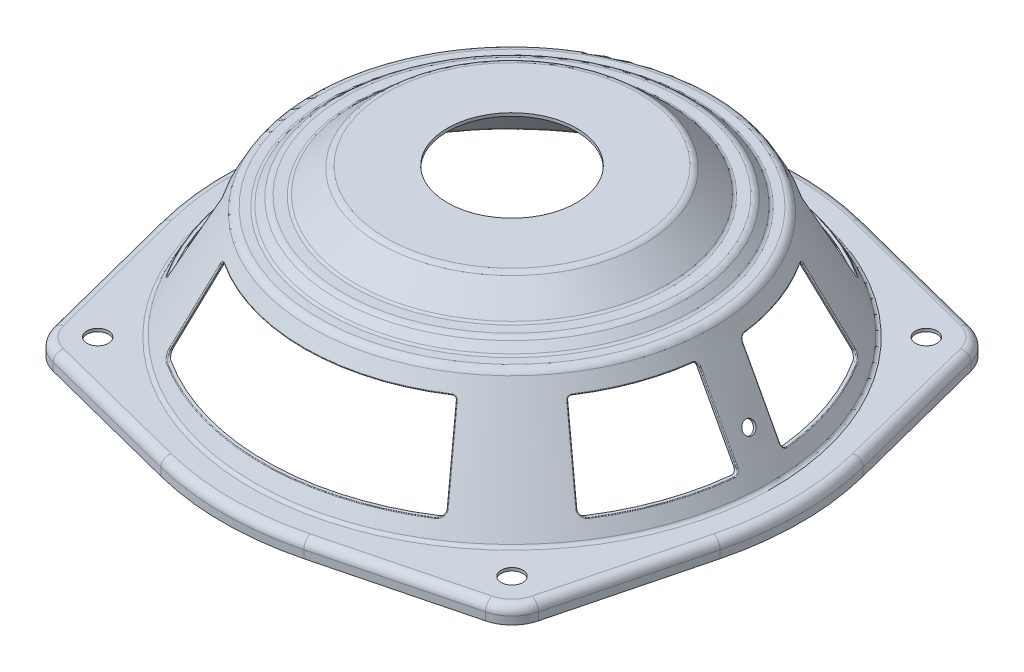
SolidWorks part; units mm, degrees
material "Простая углеродистая сталь"
ref_plane "Спереди" through (0, 0, 0) normal (0, 0, 1) x (1, 0, 0)
ref_plane "Сверху" through (0, 0, 0) normal (0, 1, 0) x (1, 0, 0)
ref_plane "Справа" through (0, 0, 0) normal (1, 0, 0) x (0, 0, -1)
sketch "Эскиз1" plane through (0, 0, 0) normal (0, 0, 1) x (1, 0, 0)
  line L0 (0, 0) -> (-30, 0)
  line L1 (-30, 0) -> (-36.5, -6)
  line L2 (-36.5, -6) -> (-40, -6)
  line L3 (-40, -6) -> (-42.5, -8.3077)
  line L4 (-42.5, -8.3077) -> (-46, -8.3077)
  line L5 (-46, -8.3077) -> (-60, -34.5)
  line L6 (-60, -34.5) -> (0, -34.5)
  line L7 (0, -34.5) -> (0, 0)
  dimension "D1" = 60
  dimension "D2" = 34.5
  dimension "D3" = 30
  dimension "D4" = 36.5
  dimension "D5" = 6
  dimension "D6" = 40
  dimension "D7" = 42.5
  dimension "D8" = 46
revolve "Повернуть1" add sketch "Эскиз1" angle 360 about L7
sketch "Эскиз2" plane through (0, -34.5, 0) normal (0, -1, 0) x (1, 0, 0)
  circle A0 centre (0, 0) radius 67
  dimension "D1" = 134
extrude "Бобышка-Вытянуть1" add sketch "Эскиз2" along normal blind 3.8
sketch "Эскиз3" plane through (0, -34.5, 0) normal (0, 1, 0) x (1, 0, 0)
  line L0 (-56.3181, -50.1899) -> (-64.9097, -16.6052)
  line L1 (-48.0833, 48.0833) -> (48.0833, 48.0833) construction
  line L2 (-48.0833, 48.0833) -> (-48.0833, -48.0833) construction
  line L3 (-48.0833, -48.0833) -> (48.0833, -48.0833) construction
  line L4 (48.0833, 48.0833) -> (48.0833, -48.0833) construction
  line L5 (-48.0833, 48.0833) -> (48.0833, -48.0833) construction
  line L6 (-48.0833, -48.0833) -> (48.0833, 48.0833) construction
  line L7 (-64.9097, 16.6052) -> (-56.3181, 50.1899)
  line L8 (-16.6052, 64.9097) -> (-50.1899, 56.3181)
  line L9 (50.1899, 56.3181) -> (16.6052, 64.9097)
  line L10 (56.3181, 50.1899) -> (64.9097, 16.6052)
  line L11 (64.9097, -16.6052) -> (56.3181, -50.1899)
  line L12 (16.6052, -64.9097) -> (50.1899, -56.3181)
  line L13 (-16.6052, -64.9097) -> (-50.1899, -56.3181)
  arc A0 (-56.3181, -50.1899) -> (-50.1899, -56.3181) centre (-48.0833, -48.0833) ccw
  arc A2 (64.9097, -16.6052) -> (64.9097, 16.6052) centre (0, 0) ccw
  arc A3 (-50.1899, 56.3181) -> (-56.3181, 50.1899) centre (-48.0833, 48.0833) ccw
  circle A4 centre (0, 0) radius 67 construction
  arc A5 (-16.6052, -64.9097) -> (16.6052, -64.9097) centre (0, 0) ccw
  arc A6 (-64.9097, 16.6052) -> (-64.9097, -16.6052) centre (0, 0) ccw
  arc A7 (16.6052, 64.9097) -> (-16.6052, 64.9097) centre (0, 0) ccw
  arc A8 (50.1899, -56.3181) -> (56.3181, -50.1899) centre (48.0833, -48.0833) ccw
  arc A9 (56.3181, 50.1899) -> (50.1899, 56.3181) centre (48.0833, 48.0833) ccw
  point P0 (0, 0)
  dimension "D1" = 8.5
  dimension "D2" = 136
extrude "Бобышка-Вытянуть2" add sketch "Эскиз3" against normal up to surface (3.8 mm away) up to face at (0, -38.3, -67)
sketch "Эскиз4" plane through (0, -38.3, 0) normal (0, -1, 0) x (1, 0, 0)
  circle A0 centre (-48.0833, 48.0833) radius 2.5
  circle A1 centre (48.0833, 48.0833) radius 2.5
  circle A2 centre (48.0833, -48.0833) radius 2.5
  circle A3 centre (-48.0833, -48.0833) radius 2.5
  dimension "D1" = 5
  dimension "D2" = 136
extrude "Вырез-Вытянуть1" cut sketch "Эскиз4" against normal through all
fillet "Скругление1" radius 2 19 edges at (-67, -34.5, 0) (-60.6139, -34.5, -33.3975) (-54.0937, -34.5, -54.0937) (-33.3975, -34.5, -60.6139) (0, -34.5, -67) (33.3975, -34.5, -60.6139) (54.0937, -34.5, -54.0937) (60.6139, -34.5, -33.3975) (67, -34.5, 0) (60.6139, -34.5, 33.3975) (54.0937, -34.5, 54.0937) (33.3975, -34.5, 60.6139) (0, -34.5, 67) (-33.3975, -34.5, 60.6139) (-54.0937, -34.5, 54.0937) (-60.6139, -34.5, 33.3975) (0, -8.3077, -46) (0, -6, -40) (0, 0, -30)
fillet "Скругление2" radius 1 3 edges at (0, -34.5, -60) (0, -8.3077, -42.5) (0, -6, -36.5)
shell "Оболочка1" thickness 0.7 removed face at (48.0833, -38.3, -50.5833) removed face at (48.0833, -38.3, 45.5833) removed face at (-48.0833, -38.3, -50.5833) removed face at (-48.0833, -38.3, 45.5833) removed face at (-48.0833, -38.3, -50.5833)
sketch "Эскиз5" plane through (0, 0, 0) normal (0, 0, 1) x (1, 0, 0)
  line L0 (-32.5, -30.8) -> (-27, -12.8)
  line L1 (-27, -12.8) -> (27, -12.8)
  line L2 (27, -12.8) -> (32.5, -30.8)
  line L3 (32.5, -30.8) -> (-32.5, -30.8)
  line L4 (-16.6052, -38.3) -> (16.6052, -38.3) construction
  point P2 (0, -12.8)
  point P5 (0, -30.8)
  dimension "D1" = 7.5
  dimension "D2" = 18
  dimension "D3" = 54
  dimension "D4" = 65
extrude "Вырез-Вытянуть2" cut sketch "Эскиз5" against normal up to next and the other way up to next
sketch "Эскиз6" plane through (0, 0, 0) normal (1, 0, 0) x (0, 0, -1)
  line L0 (-27, -12.8) -> (27, -12.8)
  line L1 (27, -12.8) -> (32.5, -30.8)
  line L2 (32.5, -30.8) -> (-32.5, -30.8)
  line L3 (-32.5, -30.8) -> (-27, -12.8)
  line L6 (57.2286, -30.8) -> (47.1048, -30.8) construction
  line L7 (39.2106, -12.8) -> (47.6075, -12.8) construction
  point P2 (0, -12.8)
  point P5 (0, -30.8)
  dimension "D1" = 54
  dimension "D2" = 65
extrude "Вырез-Вытянуть3" cut sketch "Эскиз6" against normal up to next
sketch "Эскиз7" plane through (0, 0, 0) normal (1, 0, 0) x (0, 0, -1)
  line L0 (-27, -12.8) -> (-5, -12.8)
  line L1 (-5, -12.8) -> (-5, -30.8)
  line L2 (-5, -30.8) -> (-32.5, -30.8)
  line L3 (-32.5, -30.8) -> (-27, -12.8)
  line L4 (5, -12.8) -> (27, -12.8)
  line L5 (27, -12.8) -> (32.5, -30.8)
  line L6 (32.5, -30.8) -> (5, -30.8)
  line L7 (5, -30.8) -> (5, -12.8)
  line L8 (-5, -12.8) -> (5, -12.8) construction
  line L11 (-48.4012, -12.8) -> (-40.1706, -12.8) construction
  line L12 (-47.1048, -30.8) -> (-57.2286, -30.8) construction
  point P6 (0, -12.8)
  dimension "D1" = 54
  dimension "D2" = 65
  dimension "D3" = 10
extrude "Вырез-Вытянуть4" cut sketch "Эскиз7" along normal up to next
sketch "Эскиз8" plane through (0, 0, 0) normal (0, 1, 0) x (1, 0, 0)
  circle A0 centre (0, 0) radius 15
  dimension "D1" = 30
extrude "Вырез-Вытянуть5" cut sketch "Эскиз8" against normal through all
fillet "Скругление3" radius 1 20 edges at (27, -12.8, -39.6906) (32.5, -30.8, -47.5854) (-32.5, -30.8, -47.5854) (-27, -12.8, -39.6906) (-27, -12.8, 39.6906) (27, -12.8, 39.6906) (32.5, -30.8, 47.5854) (-32.5, -30.8, 47.5854) (39.6906, -12.8, 27) (47.7432, -12.8, -5) (39.6906, -12.8, -27) (47.7432, -12.8, 5) (57.4081, -30.8, 5) (47.5854, -30.8, -32.5) (57.4081, -30.8, -5) (47.5854, -30.8, 32.5) (-47.5854, -30.8, -32.5) (-39.6906, -12.8, -27) (-39.6906, -12.8, 27) (-47.5854, -30.8, 32.5)
fillet "Скругление4" radius 0.2 40 edges at (31.9024, -30.4573, -48.2452) (0, -30.8, -58.0223) (-32.059, -30.2142, -47.9852) (47.9852, -30.2142, -32.059) (48.2424, -13.0532, -5.3349) (57.5903, -30.4346, -5.2271) (54.7942, -30.8, -19.0837) (-31.9024, -30.4573, 48.2452) (0, -30.8, 58.0223) (32.059, -30.2142, 47.9852) (-48.2452, -30.4573, -31.9024) (-58.0223, -30.8, 0) (-47.9852, -30.2142, 32.059) (57.6128, -30.4839, 5.2704) (48.2003, -12.991, 5.4123) (48.2452, -30.4573, 31.9024) (54.7942, -30.8, 19.0837) (40.4047, -12.9616, -26.805) (45.4854, -12.8, -16.5455) (26.805, -12.9616, 40.4047) (0, -12.8, 48.4012) (-26.9427, -13.0694, 40.3822) (-26.805, -12.9616, -40.4047) (0, -12.8, -48.4012) (26.9427, -13.0694, -40.3822) (-40.3822, -13.0694, -26.9427) (-40.4047, -12.9616, 26.805) (-48.4012, -12.8, 0) (45.4854, -12.8, 16.5455) (40.3822, -13.0694, 26.9427)
ref_plane "Плоскость1" through (31.4136, 16.8683, 0) normal (0.881, 0.4731, 0) x (0, 0, -1)
sketch "Эскиз9" plane through (31.4136, 16.8683, 0) normal (0.881, 0.4731, 0) x (0, 0, -1)
  line L0 (-5, -44.1687) -> (5, -44.1687) construction
  line L1 (-5, -35.0892) -> (-5, -53.2482) construction
  line L2 (5, -53.2482) -> (5, -35.0892) construction
  line L3 (5, -44.1687) -> (0, -48.1687) construction
  line L4 (0, -48.1687) -> (0, -44.1687) construction
  circle A0 centre (0, -48.1687) radius 1.5
  dimension "D1" = 3
  dimension "D2" = 4
extrude "Вырез-Вытянуть6" cut sketch "Эскиз9" along normal up to next
